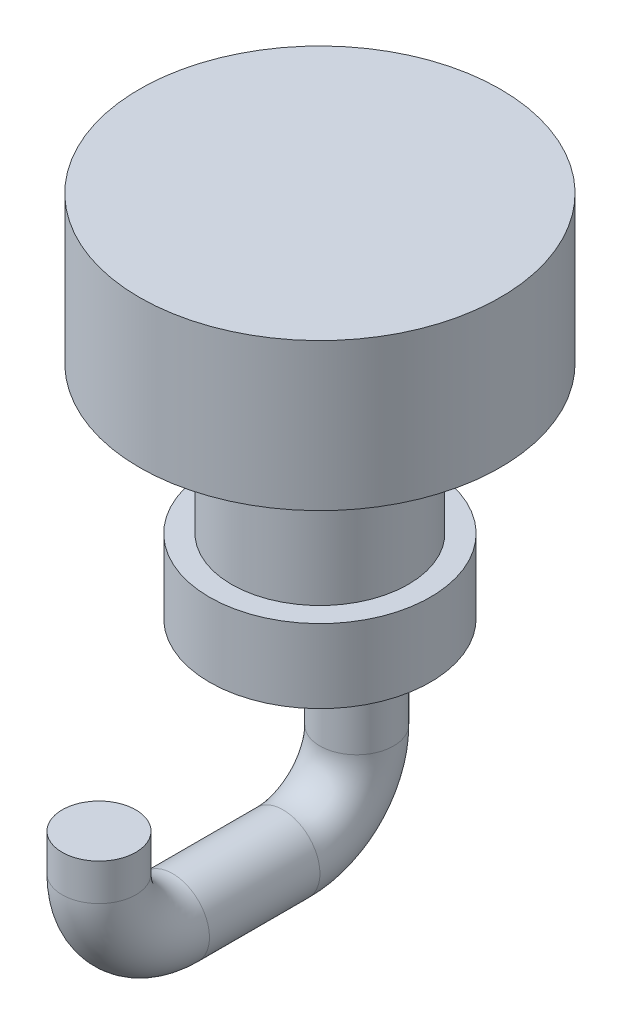
SolidWorks part; units mm, degrees
ref_plane "Front Plane" through (0, 0, 0) normal (0, 0, 1) x (1, 0, 0)
ref_plane "Top Plane" through (0, 0, 0) normal (0, 1, 0) x (1, 0, 0)
ref_plane "Right Plane" through (0, 0, 0) normal (1, 0, 0) x (0, 0, -1)
sketch "Sketch1" plane through (0, 0, 0) normal (0, 0, 1) x (1, 0, 0)
  line L0 (0, 0) -> (6.223, 0)
  line L1 (6.223, 0) -> (6.223, -5.08)
  line L2 (6.223, -5.08) -> (3.048, -5.08)
  line L3 (3.048, -5.08) -> (3.048, -10.16)
  line L4 (3.048, -10.16) -> (3.81, -10.16)
  line L5 (3.81, -10.16) -> (3.81, -12.7)
  line L6 (3.81, -12.7) -> (0, -12.7)
  line L7 (0, -12.7) -> (0, 0)
  dimension "D1" = 12.7
  dimension "D2" = 2.54
  dimension "D3" = 5.08
  dimension "D4" = 6.223
  dimension "D5" = 3.048
  dimension "D6" = 3.81
revolve "button body" add sketch "Sketch1" angle 360 about L7
ref_plane "spring path" through (4.318, 0, 0) normal (1, 0, 0) x (0, 0, -1)
sketch "Sketch2" plane through (4.318, 0, 0) normal (1, 0, 0) x (0, 0, -1)
  spline S0 degree 3 poles (2.9542, -4.563) (1.8538, -5.2739) (-1.4839, -5.7786) (3.0242, -6.9827) knots 0 0 0 0 1 1 1 1
ref_plane "spring cross section" through (0, 0, -3.0242) normal (0, 0, 1) x (1, 0, 0)
ref_axis "center axis" through (0, 0, 0) along (0, -1, 0)
pattern_circular "moar springs" count 4 over 360 about axis through (0, 0, 0) along (0, -1, 0) of bodies 101 102
ref_plane "curve hook" through (0, 0, 0) normal (0, 0, 1) x (1, 0, 0)
ref_point "curve start"
ref_plane "hook plane" through (0, 0, 0) normal (1, 0, 0) x (0, 0, -1)
sketch "Sketch12" plane through (0, 0, 0) normal (1, 0, 0) x (0, 0, -1)
  line L0 (0, -12.7) -> (0, -16.51)
  line L1 (-1.27, -17.78) -> (-5.08, -17.78)
  line L2 (-6.35, -16.51) -> (-6.35, -15.24)
  arc A0 (0, -16.51) -> (-1.27, -17.78) centre (-1.27, -16.51) cw
  arc A1 (-5.08, -17.78) -> (-6.35, -16.51) centre (-5.08, -16.51) cw
  point P8 (0, -17.78)
  point P11 (-6.35, -17.78)
  dimension "D2" = 1.27
  dimension "D4" = 1.27
  dimension "D1" = 5.08
  dimension "D3" = 2.54
  dimension "D5" = 3.81
sketch "Sketch13" plane through (0, -12.7, 0) normal (0, -1, 0) x (-1, 0, 0)
  circle A0 centre (0, 1.27) radius 1.27
sweep "hook for baton" add profiles "Sketch13" path "Sketch12"
